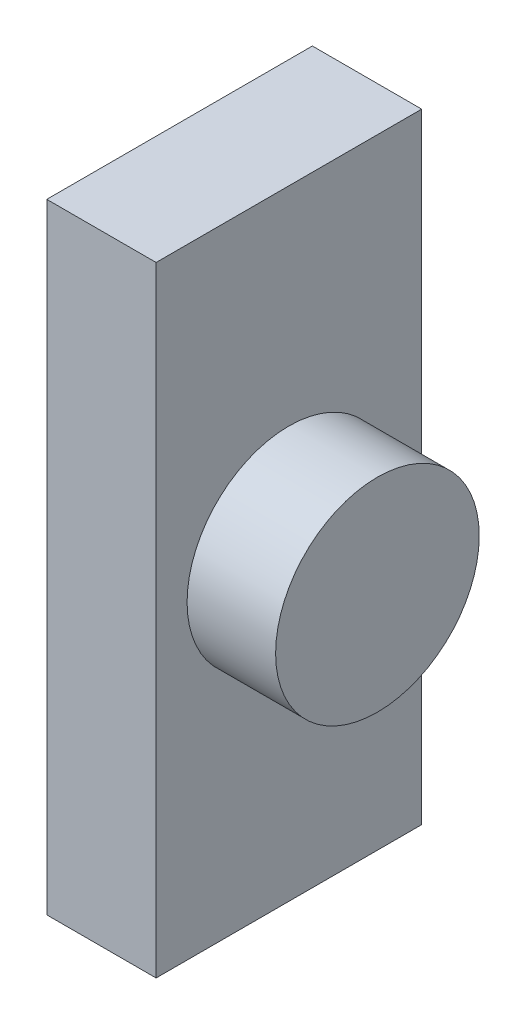
SolidWorks part; units mm, degrees
ref_plane "Front Plane" through (0, 0, 0) normal (0, 0, 1) x (1, 0, 0)
ref_plane "Top Plane" through (0, 0, 0) normal (0, 1, 0) x (1, 0, 0)
ref_plane "Right Plane" through (0, 0, 0) normal (1, 0, 0) x (0, 0, -1)
sketch "Sketch1" plane through (0, 0, 0) normal (1, 0, 0) x (0, 0, -1)
  line L0 (5.8125, 17.5) -> (9.1875, 17.5) construction
  line L1 (5.8125, 26) -> (9.1875, 26)
  line L2 (5.8125, 26) -> (5.8125, 9)
  line L3 (5.8125, 9) -> (9.1875, 9)
  line L4 (9.1875, 26) -> (9.1875, 9)
  line L5 (7.5, 26) -> (7.5, 9) construction
  line L6 (7.5, 35) -> (7.5, 0) construction
  line L15 (0, 35) -> (15, 35)
  line L16 (0, 35) -> (0, 0)
  line L17 (0, 0) -> (15, 0)
  line L18 (15, 35) -> (15, 0)
  line L19 (0, 17.5) -> (15, 17.5) construction
  dimension "D2" = 3.375
  dimension "D3" = 17
  dimension "D4" = 15
  dimension "D5" = 35
extrude "Boss-Extrude1" add sketch "Sketch1" along normal blind 4.175
sketch "Sketch2" plane through (4.175, 0, 0) normal (1, 0, 0) x (0, 0, -1)
  line L1 (0, 35) -> (15, 35)
  line L2 (0, 35) -> (0, 0)
  line L3 (0, 0) -> (15, 0)
  line L4 (15, 35) -> (15, 0)
extrude "Boss-Extrude2" add sketch "Sketch2" along normal blind 2
sketch "Sketch3" plane through (6.175, 0, 0) normal (1, 0, 0) x (0, 0, -1)
  line L0 (7.5, 35) -> (7.5, 0) construction
  line L1 (15, 35) -> (0, 35) construction
  line L2 (0, 0) -> (15, 0) construction
  line L3 (0, 17.5) -> (15, 17.5) construction
  line L4 (0, 35) -> (0, 0) construction
  line L5 (15, 0) -> (15, 35) construction
  circle A0 centre (7.5, 17.5) radius 5.75
  dimension "D1" = 11.5
extrude "Boss-Extrude3" add sketch "Sketch3" along normal blind 5
